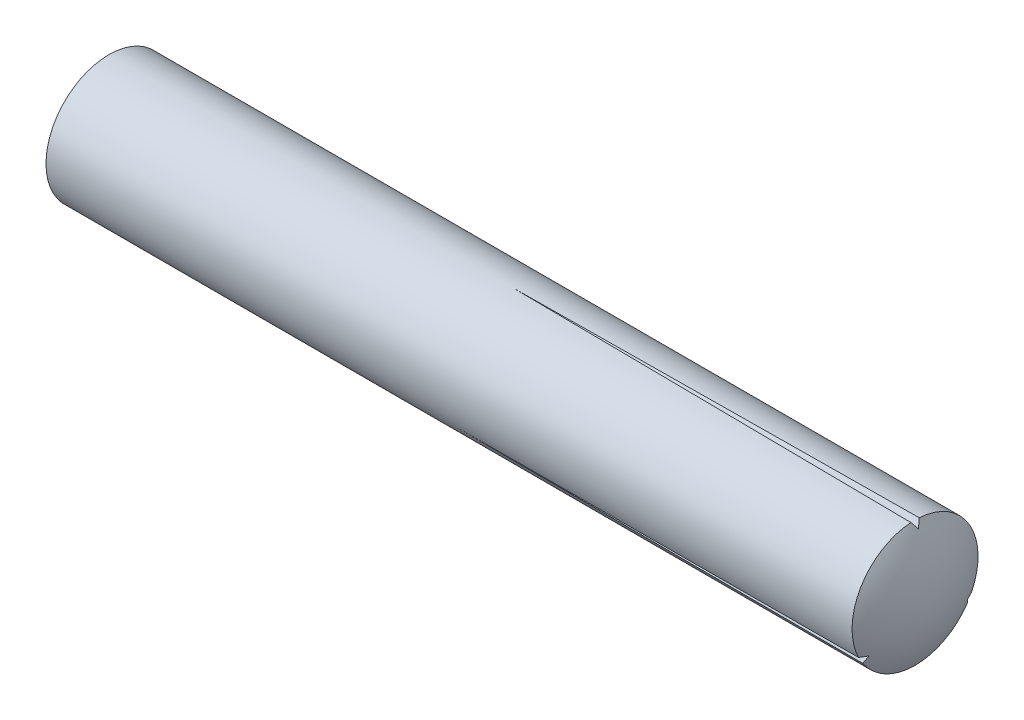
SolidWorks part; units mm, degrees
ref_plane "Front" through (0, 0, 0) normal (0, 0, 1) x (1, 0, 0)
ref_plane "Top" through (0, 0, 0) normal (0, 1, 0) x (1, 0, 0)
ref_plane "Right" through (0, 0, 0) normal (1, 0, 0) x (0, 0, -1)
sketch "Sketch1" plane through (0, 0, 0) normal (0, 0, 1) x (1, 0, 0)
  line L0 (10, 0) -> (0, 0)
  line L1 (0.201, 0.75) -> (9.799, 0.75)
  line L2 (-11.7496, 0) -> (1.4496, 0) construction
  arc A0 (0.201, 0.75) -> (0, 0) centre (1.5, 0) ccw
  arc A1 (9.799, 0.75) -> (10, 0) centre (8.5, 0) cw
revolve "Base-Revolve" add sketch "Sketch1" angle 360 about L2
ref_plane "Plane1" through (10, 0, 0) normal (1, 0, 0) x (0, 0, -1)
sketch "Sketch2" plane through (10, 0, 0) normal (1, 0, 0) x (0, 0, -1)
  line L0 (-0.0525, 0.75) -> (0, 0.675)
  line L1 (0, 0.675) -> (0.0525, 0.75)
  line L2 (-0.0525, 0.75) -> (0.0525, 0.75)
  line L3 (0, 0.9637) -> (0, -0.1519) construction
  dimension "D1" = 70
  dimension "D2" = 35
  dimension "D3" = 0.75
  dimension "D4" = 0.675
sketch "Sketch3" plane through (0, 0, 0) normal (1, 0, 0) x (0, 0, -1)
  point P0 (0, 0.75)
  dimension "D1" = 0.75
loft "Cut-Loft1" [suppressed] cut profiles "Sketch2", "Sketch3"
pattern_circular "CirPattern1" [suppressed] count 3 over 360 about axis through (-11.7496, 0, 0) along (1, 0, 0) of bodies 102
ref_plane "Plane2" through (5, 0, 0) normal (1, 0, 0) x (0, 0, -1)
sketch "Sketch5" plane through (5, 0, 0) normal (1, 0, 0) x (0, 0, -1)
  point P0 (0, 0.75)
  dimension "D1" = 0.75
sketch "Sketch4" plane through (10, 0, 0) normal (1, 0, 0) x (0, 0, -1)
  line L0 (-0.0525, 0.75) -> (0, 0.675)
  line L1 (0, 0.675) -> (0.0525, 0.75)
  line L2 (0.0525, 0.75) -> (-0.0525, 0.75)
  line L3 (0, 0.8531) -> (0, -0.1202) construction
  dimension "D1" = 70
  dimension "D2" = 35
  dimension "D4" = 0.675
  dimension "D3" = 0.75
loft "Cut-Loft2" cut profiles "Sketch5", "Sketch4"
pattern_circular "CirPattern2" count 3 over 360 about axis through (-11.7496, 0, 0) along (1, 0, 0) of "Cut-Loft2"
equation "\"r@Sketch1\" = \"d@Sketch1\""
equation "\"D3@Sketch2\" = \"d@Sketch1\" / 2"
equation "\"D4@Sketch2\" = \"D3@Sketch2\" * 0.9"
equation "\"D1@Sketch3\" = \"d@Sketch1\" / 2"
equation "\"D3@Sketch4\" = \"d@Sketch1\" / 2"
equation "\"D4@Sketch4\" = \"D3@Sketch4\" * 0.9"
equation "\"D1@Sketch5\" = \"d@Sketch1\" / 2"
